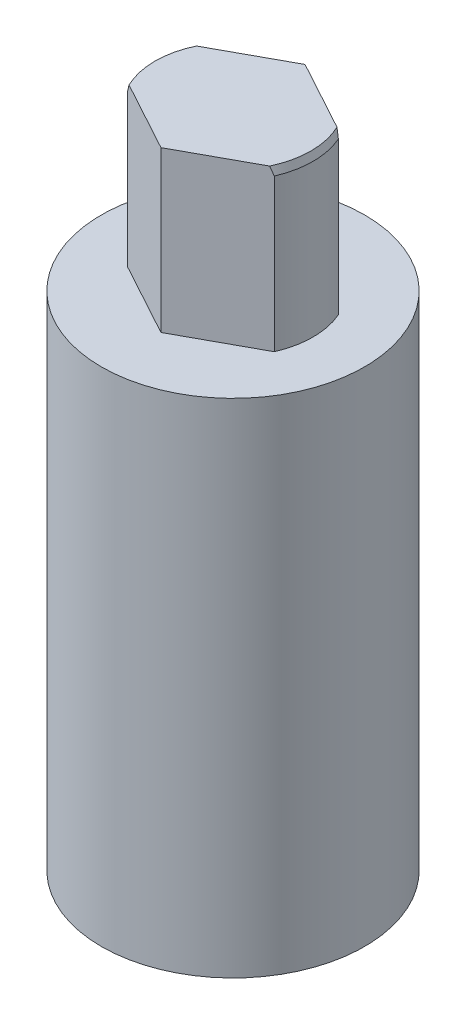
SolidWorks part; units mm, degrees
ref_plane "Спереди" through (0, 0, 0) normal (0, 0, 1) x (1, 0, 0)
ref_plane "Сверху" through (0, 0, 0) normal (0, 1, 0) x (1, 0, 0)
ref_plane "Справа" through (0, 0, 0) normal (1, 0, 0) x (0, 0, -1)
sketch "Эскиз1" plane through (0, 0, 0) normal (0, 1, 0) x (1, 0, 0)
  circle A0 centre (0, 0) radius 10.0871
  dimension "D1" = 20.1742
extrude "Бобышка-Вытянуть1" add sketch "Эскиз1" along normal blind 20.1742
sketch "Эскиз2" plane through (0, 0, 0) normal (0, -1, 0) x (1, 0, 0)
  circle A0 centre (0, 0) radius 16.5871
  dimension "D1" = 33.1742
extrude "Бобышка-Вытянуть2" add sketch "Эскиз2" along normal blind 63.26
chamfer "Фаска1" distance 1 angle 15 1 edges at (0, 20.1742, 10.0871) first distance on face at (0, 20.1742, 10.0871)
sketch "Эскиз4" plane through (0, 20.1742, 0) normal (0, 1, 0) x (1, 0, 0)
  line L0 (-9.245, 4.0348) -> (0, 9.0784)
  line L1 (0, 8.1024) -> (0, -5.8491) construction
  line L2 (0, -9.0784) -> (9.245, -4.0348)
  line L3 (0, -9.0784) -> (-9.245, -4.0348)
  line L4 (9.245, 4.0348) -> (0, 9.0784)
  line L5 (-5.6333, 0) -> (6.6401, 0) construction
  arc A0 (-9.245, -4.0348) -> (-9.245, 4.0348) centre (0, 0) cw
  arc A1 (9.245, -4.0348) -> (9.245, 4.0348) centre (0, 0) ccw
  circle A2 centre (0, 0) radius 10.0871 construction
  dimension "D1" = 18.1568
  dimension "D2" = 8.0697
extrude "Вырез-Вытянуть2" cut sketch "Эскиз4" against normal blind 20.1742 flip side to cut
ref_axis "SettingUpAxis" through (0, 34.4851, 0) along (0, -1, 0)
ref_plane "SettingUpPlaneVertical" through (0, 0, 0) normal (-1, 0, 0) x (0, 0, 1)
ref_plane "SettingPlane" through (0, 0, 0) normal (0, -1, 0) x (-1, 0, 0)
equation "\"ReferenceDimensionHight\"=63.26"
equation "\"ReferenceDimensionDiameter\"= 20.174241"
equation "\"D1@Эскиз1\" = \"ReferenceDimensionDiameter\""
equation "\"D1@Эскиз2\" = \"D1@Эскиз1\" + \"ReferenceDimensionWidthBurt\""
equation "\"D1@Эскиз4\"=\"ReferenceDimensionDiameter\"*0.9"
equation "\"D1@Бобышка-Вытянуть1\" = \"ReferenceDimensionLength\""
equation "\"ReferenceDimensionWidthBurt\"= 13"
equation "\"D1@Вырез-Вытянуть2\"=\"D1@Бобышка-Вытянуть1\""
equation "\"ReferenceDimensionLength\"= \"ReferenceDimensionDiameter\""
equation "\"D1@Бобышка-Вытянуть2\"=\"ReferenceDimensionHight\""
equation "\"D2@Эскиз4\"=\"ReferenceDimensionDiameter\"*0.4"
